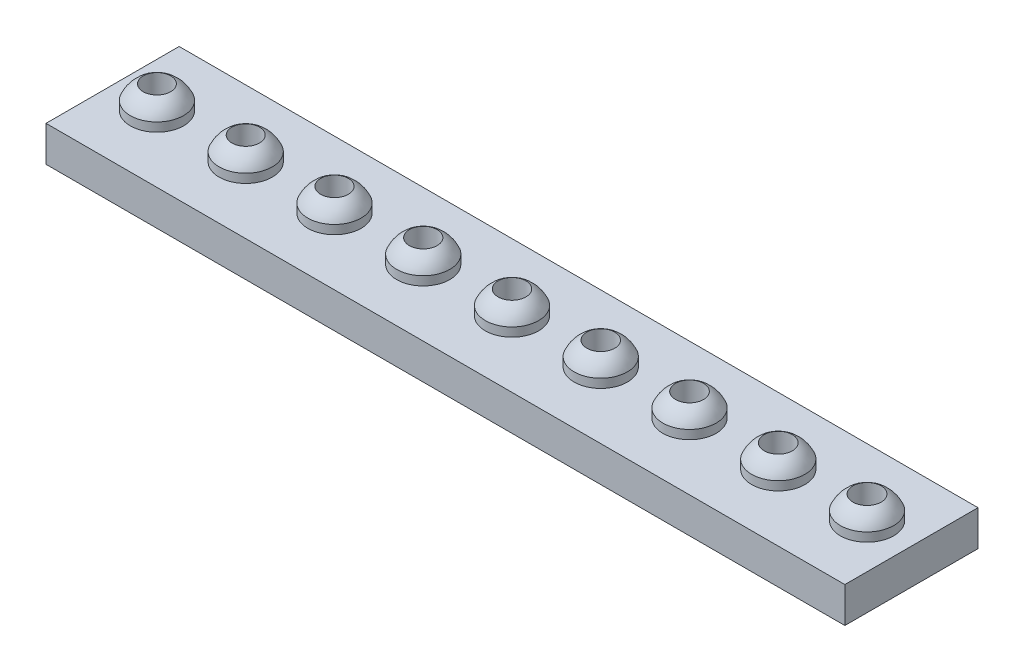
SolidWorks part; units mm, degrees
ref_plane "Front Plane" through (0, 0, 0) normal (0, 0, 1) x (1, 0, 0)
ref_plane "Top Plane" through (0, 0, 0) normal (0, 1, 0) x (1, 0, 0)
ref_plane "Right Plane" through (0, 0, 0) normal (1, 0, 0) x (0, 0, -1)
sketch "Sketch1" plane through (0, 0, 0) normal (0, 1, 0) x (1, 0, 0)
  line L1 (0, 0) -> (90, 0)
  line L2 (0, 0) -> (0, -15)
  line L3 (0, -15) -> (90, -15)
  line L4 (90, 0) -> (90, -15)
  dimension "D1" = 15
  dimension "D2" = 90
extrude "Boss-Extrude1" add sketch "Sketch1" along normal blind 4 contours L3 L4 L1 L2
sketch "Sketch2" plane through (0, 4, 0) normal (0, 1, 0) x (1, 0, 0)
  line L0 (0, -7.5) -> (90, -7.5) construction
  line L1 (0, 0) -> (0, -15) construction
  line L2 (90, 0) -> (90, -15) construction
  circle A0 centre (45, -7.5) radius 3
  dimension "D1" = 6
extrude "Boss-Extrude2" add sketch "Sketch2" along normal blind 1
dome "Dome1" faces to dome 1 distance 2 reverse direction no elliptical dome no face at (45, 5, 10.5) parameters "D1"=2
pattern_linear "LPattern1" count 5 spacing 10 along (-1, 0, 0) count 5 spacing 10 along (1, 0, 0) of "Boss-Extrude2", "Dome1" pattern seed only yes
sketch "Sketch3" plane through (0, 4, 0) normal (0, 1, 0) x (1, 0, 0)
  circle A0 centre (5, -7.5) radius 1.55
  circle A2 centre (15, -7.5) radius 1.555
  circle A3 centre (25, -7.5) radius 1.56
  circle A4 centre (35, -7.5) radius 1.565
  circle A5 centre (45, -7.5) radius 1.57
  circle A6 centre (55, -7.5) radius 1.575
  circle A7 centre (65, -7.5) radius 1.58
  circle A8 centre (75, -7.5) radius 1.585
  circle A9 centre (85, -7.5) radius 1.59
  dimension "D1" = 3.1
  dimension "D2" = 3.11
  dimension "D3" = 3.12
  dimension "D4" = 3.13
  dimension "D5" = 3.14
  dimension "D6" = 3.15
  dimension "D7" = 3.16
  dimension "D8" = 3.17
  dimension "D9" = 3.18
extrude "Cut-Extrude2" cut sketch "Sketch3" against normal up to next and the other way up to next contours A0 | A2 | A3 | A4 | A5 | A6 | A7 | A8 | A9
